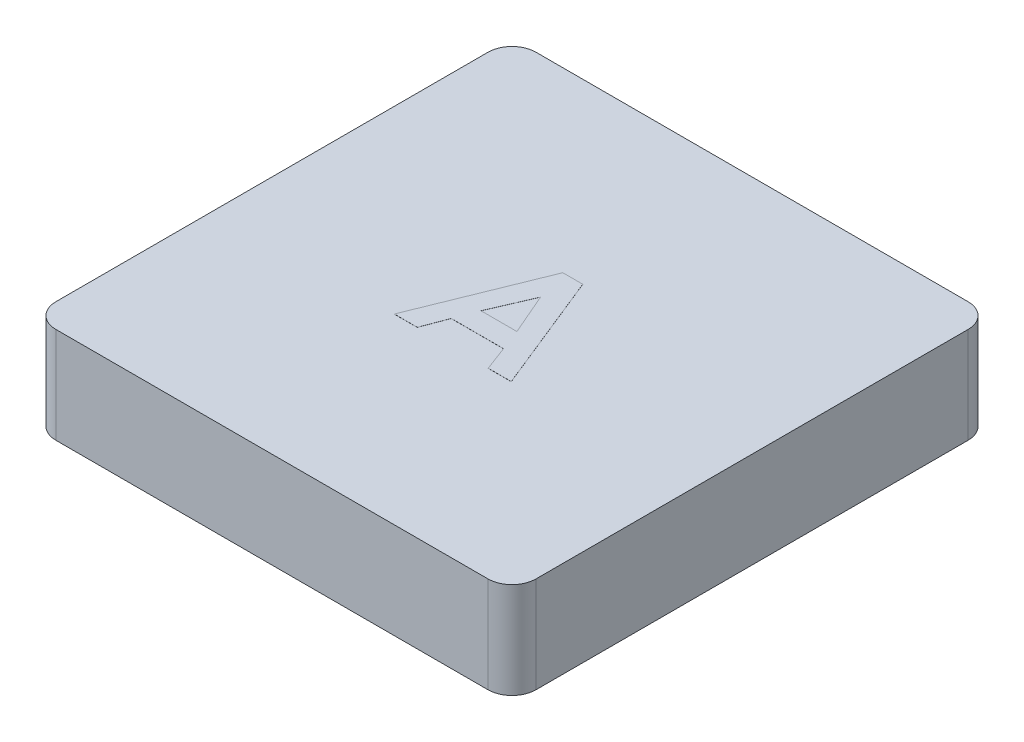
SolidWorks part; units mm, degrees
ref_plane "Front Plane" through (0, 0, 0) normal (0, 0, 1) x (1, 0, 0)
ref_plane "Top Plane" through (0, 0, 0) normal (0, 1, 0) x (1, 0, 0)
ref_plane "Right Plane" through (0, 0, 0) normal (1, 0, 0) x (0, 0, -1)
sketch "Sketch1" plane through (0, 0, 0) normal (0, 1, 0) x (1, 0, 0)
  line L0 (0, 0) -> (12.7, 0)
  line L1 (12.7, 0) -> (12.7, 12.7)
  line L2 (12.7, 12.7) -> (0, 12.7)
  line L3 (0, 12.7) -> (0, 0)
  dimension "D1" = 12.7
  dimension "D2" = 12.7
extrude "Boss-Extrude1" add sketch "Sketch1" along normal blind 2.54
fillet "Fillet1" radius 0.635 4 edges at (0, 1.27, -12.7) (12.7, 1.27, -12.7) (12.7, 1.27, 0) (0, 1.27, 0)
shell "Shell1" thickness 0.635 removed face at (6.35, 0, -6.35)
sketch "Sketch2" plane through (0, 1.905, 0) normal (0, -1, 0) x (-1, 0, 0)
  line L0 (-0.635, 6.35) -> (-12.065, 6.35) construction
  line L1 (-0.635, 12.065) -> (-0.635, 0.635) construction
  line L2 (-12.065, 0.635) -> (-12.065, 12.065) construction
  line L3 (-6.35, 0.635) -> (-6.35, 12.065) construction
  line L4 (-0.635, 0.635) -> (-12.065, 0.635) construction
  line L5 (-12.065, 12.065) -> (-0.635, 12.065) construction
  circle A0 centre (-6.35, 6.35) radius 2.54
  dimension "D1" = 5.08
extrude "Boss-Extrude2" add sketch "Sketch2" along normal up to surface (1.905 mm away) up to face at (6.35, 0, -6.35)
sketch "Sketch3" plane through (0, 2.54, 0) normal (0, 1, 0) x (1, 0, 0)
  line L0 (0, 12.065) -> (0, 0.635) construction
  line L1 (0.635, 0) -> (12.065, 0) construction
  text T0 "<b>A</b>"
  point P1 (0, 0)
  dimension "D1" = 4.699
  dimension "D2" = 4.826
extrude "Boss-Extrude3" add sketch "Sketch3" along normal blind 0.0025
